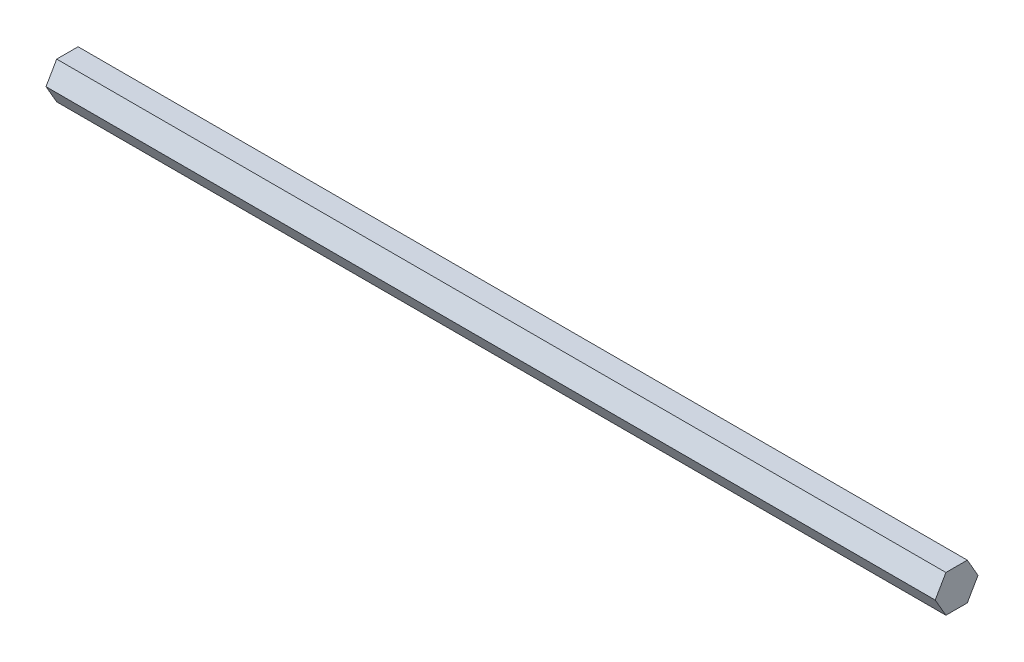
SolidWorks part; units mm, degrees
material "7075-T6 (SN)"
ref_plane "Front Plane" through (0, 0, 0) normal (0, 0, 1) x (1, 0, 0)
ref_plane "Top Plane" through (0, 0, 0) normal (0, 1, 0) x (1, 0, 0)
ref_plane "Right Plane" through (0, 0, 0) normal (1, 0, 0) x (0, 0, -1)
sketch "Sketch1" plane through (0, 0, 0) normal (1, 0, 0) x (0, 0, -1)
  line L1 (3.6662, 6.35) -> (-3.6662, 6.35)
  line L2 (-3.6662, 6.35) -> (-7.3323, 0)
  line L3 (-7.3323, 0) -> (-3.6662, -6.35)
  line L4 (-3.6662, -6.35) -> (3.6662, -6.35)
  line L5 (3.6662, -6.35) -> (7.3323, 0)
  line L6 (7.3323, 0) -> (3.6662, 6.35)
  circle A0 centre (0, 0) radius 6.35 construction
  dimension "D1" = 12.7
extrude "Boss-Extrude1" add sketch "Sketch1" along normal mid plane 304.8
ref_axis "Axis1" through (-167.64, 0, 0) along (1, 0, 0)
